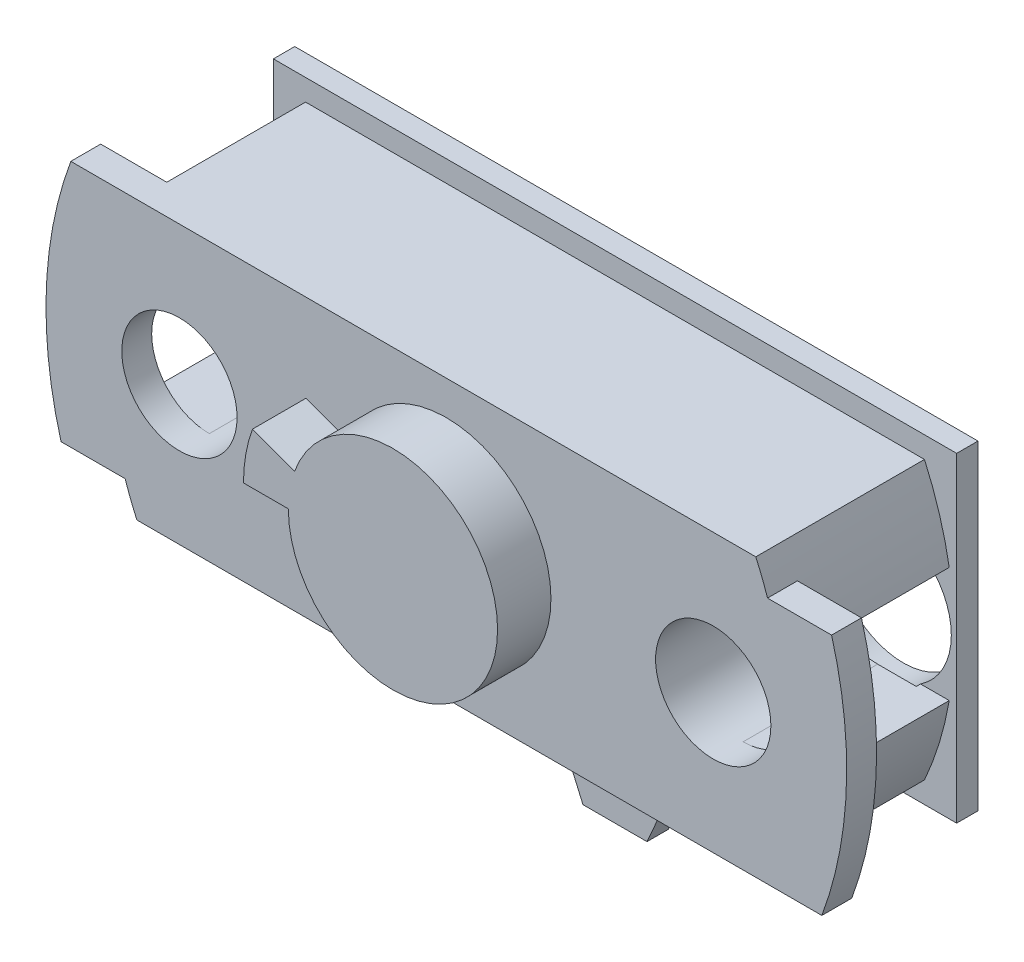
SolidWorks part; units mm, degrees
ref_plane "Přední rovina" through (0, 0, 0) normal (0, 0, 1) x (1, 0, 0)
ref_plane "Horní rovina" through (0, 0, 0) normal (0, 1, 0) x (1, 0, 0)
ref_plane "Pravá rovina" through (0, 0, 0) normal (1, 0, 0) x (0, 0, -1)
sketch "Skica1" plane through (0, 0, 0) normal (0, 0, 1) x (1, 0, 0)
  line L0 (-17.5873, 6.5) -> (17.5873, 6.5)
  line L1 (-17.5873, -6.5) -> (17.5873, -6.5)
  line L2 (-18.0431, 5.1) -> (-15.0431, 5.1)
  line L3 (-15.0431, 5.1) -> (-15.0431, 6.5)
  line L4 (18.0431, -5.1) -> (15.0431, -5.1)
  line L5 (15.0431, -5.1) -> (15.0431, -6.5)
  line L6 (-18.0431, -5.1) -> (-15.0431, -5.1)
  line L7 (-15.0431, -5.1) -> (-15.0431, -6.5)
  line L8 (18.0431, 5.1) -> (15.0431, 5.1)
  line L9 (15.0431, 5.1) -> (15.0431, 6.5)
  arc A0 (-17.5873, 6.5) -> (-17.5873, -6.5) centre (0, 0) ccw
  arc A1 (17.5873, -6.5) -> (17.5873, 6.5) centre (0, 0) ccw
  dimension "D1" = 37.5
  dimension "D2" = 13
  dimension "D3" = 1.4
  dimension "D4" = 1.4
  dimension "D5" = 3
  dimension "D6" = 3
extrude "Přidat vysunutím1" add sketch "Skica1" along normal blind 1.4 contours L4 A1 L0 L3 L2 A0 L1 L5 | L0 A0 L2 L3 | L1 A1 L4 L5 region at (-16.4373, 5.7809, 0) region at (0, 0, 0) region at (16.4373, -5.7809, 0)
sketch "Skica2" plane through (0, 0, 1.4) normal (0, 0, 1) x (1, 0, 0)
  line L0 (0, 0) -> (-6.5778, 2.3941)
  line L1 (0, 0) -> (-7, 0)
  circle A0 centre (0, 0) radius 4.9
  circle A1 centre (0, 0) radius 7
  dimension "D1" = 9.8
  dimension "D2" = 14
  dimension "D3" = 20
extrude "Přidat vysunutím2" add sketch "Skica2" along normal blind 2.5 contours L1 A0 L0 | L0 A0 L1 | L0 A1 L1 A0 region at (-3.2007, 0.5644, 1.4) region at (0.1883, -0.0332, 1.4) region at (-5.8904, 1.0386, 1.4)
sketch "Skica3" plane through (0, 0, 1.4) normal (0, 0, 1) x (1, 0, 0)
  circle A0 centre (-12.5, 0) radius 2.7
  circle A1 centre (12.5, 0) radius 2.7
  dimension "D1" = 5.4
  dimension "D2" = 5.4
  dimension "D3" = 25
  dimension "D4" = 12.5
extrude "Odebrat vysunutím1" cut sketch "Skica3" against normal blind 2.5
sketch "Skica4" plane through (0, 0, 0) normal (0, 0, -1) x (-1, 0, 0)
  line L0 (-14.4932, 6.5) -> (14.4932, 6.5)
  line L1 (17.5873, 6.5) -> (-15.0431, 6.5) construction
  line L2 (-14.4932, -6.5) -> (14.4932, -6.5)
  line L3 (15.0431, -6.5) -> (-17.5873, -6.5) construction
  line L4 (-12.5, 2.7) -> (-15.6529, 2.7)
  line L5 (-12.5, -2.7) -> (-15.6529, -2.7)
  line L6 (12.5, 2.7) -> (15.6529, 2.7)
  line L7 (12.5, -2.7) -> (15.6529, -2.7)
  arc A0 (-14.4932, 6.5) -> (-14.4932, -6.5) centre (0, 0) ccw
  arc A1 (14.4932, -6.5) -> (14.4932, 6.5) centre (0, 0) ccw
  circle A2 centre (-12.5, 0) radius 2.7
  circle A3 centre (12.5, 0) radius 2.7
  circle A4 centre (-12.5, 0) radius 2.7 construction
  circle M6 centre (12.5, 0) radius 2.7
  circle M7 centre (-12.5, 0) radius 2.7
  line M8 (17.5873, 6.5) -> (-15.0431, 6.5)
  line M12 (-17.5873, -6.5) -> (15.0431, -6.5)
extrude "Přidat vysunutím3" add sketch "Skica4" along normal blind 7.5 contours L6 A1 A0 L4 L5 L7 M8 M7 M12 M6 region at (0, 0, 0)
sketch "Skica5" plane through (0, 0, 0) normal (0, 0, -1) x (-1, 0, 0)
  line L0 (-14.4932, 6.5) -> (-15.0431, 6.5)
  line L1 (-15.0431, 6.5) -> (-15.0431, 5.1)
  line L2 (14.4932, -6.5) -> (15.0431, -6.5)
  line L3 (15.0431, -6.5) -> (15.0431, -5.1)
  circle A0 centre (0, 0) radius 15.8841
extrude "Odebrat vysunutím2" cut sketch "Skica5" against normal blind 7.5 contours A0 L2 L3 | A0 L0 L1 region at (14.8639, 6.0446, 0) region at (-14.8639, -6.0446, 0)
sketch "Skica9" plane through (0, 0, -7.5) normal (0, 0, -1) x (-1, 0, 0)
  line L0 (14.4932, 6.5) -> (-14.4932, 6.5) construction
  line L1 (-16, 7.5) -> (16, 7.5)
  line L2 (-16, 7.5) -> (-16, -7.5)
  line L3 (-16, -7.5) -> (16, -7.5)
  line L4 (16, 7.5) -> (16, -7.5)
  line L5 (-14.4932, -6.5) -> (14.4932, -6.5) construction
  line L6 (0, 0) -> (0, 7.5) construction
  dimension "D1" = 32
  dimension "D2" = 1
  dimension "D3" = 1
extrude "Přidat vysunutím5" add sketch "Skica9" against normal blind 1
sketch "Skica6" plane through (0, 0, -7.5) normal (0, 0, -1) x (-1, 0, 0)
  circle A0 centre (-12.5, 0) radius 3.25
  circle A1 centre (12.5, 0) radius 3.25
  dimension "D1" = 6.5
  dimension "D2" = 6.5
extrude "Odebrat vysunutím3" cut sketch "Skica6" against normal blind 1.2
sketch "Skica7" plane through (0, 0, -7.5) normal (0, 0, -1) x (-1, 0, 0)
  line L0 (-10.0833, -4.829) -> (10.0833, 4.829) construction
  line L2 (0, 0) -> (0, 7.5) construction
  line L3 (16, 7.5) -> (-16, 7.5) construction
  circle A0 centre (10.0833, 4.829) radius 0.95
  circle A1 centre (-10.0833, -4.829) radius 0.95
  circle A2 centre (-12.5, 0) radius 3.25 construction
  arc A3 (-14.309, -2.7) -> (-14.309, 2.7) centre (-12.5, 0) ccw construction
  point P18 (0, 0)
  point P19 (0, 0)
  dimension "D1" = 1.9
  dimension "D2" = 1.9
  dimension "D3" = 22.36
  dimension "D4" = 5.4
extrude "Odebrat vysunutím5" cut sketch "Skica7" against normal blind 7
sketch "Skica12" plane through (0, 0, -7.5) normal (0, 0, -1) x (-1, 0, 0)
  line L0 (-5, -7.5) -> (-1.5, -15.5)
  line L1 (-16, -7.5) -> (16, -7.5) construction
  line L2 (-1.5, -15.5) -> (1.5, -15.5)
  line L3 (1.5, -15.5) -> (5, -7.5)
  line L5 (-5, -7.5) -> (5, -7.5)
  point P4 (0, -15.5)
  point P7 (0, -7.5)
  dimension "D1" = 8
  dimension "D2" = 3
  dimension "D3" = 10
  dimension "D4" = 5
extrude "Přidat vysunutím7" add sketch "Skica12" against normal blind 1 contours L3 L5 L0 L2
